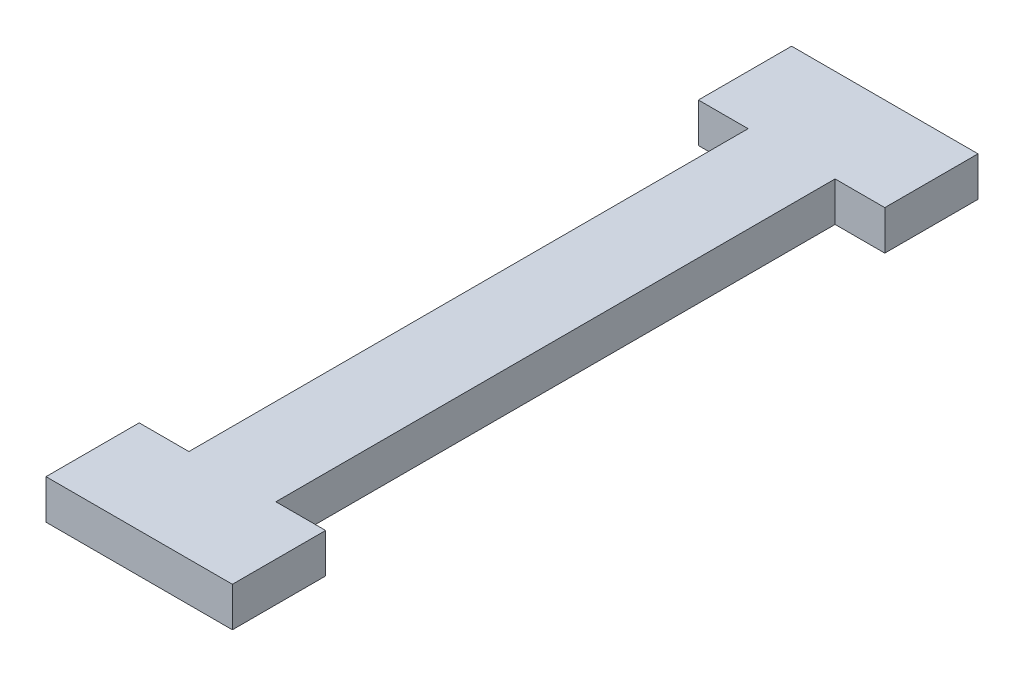
SolidWorks part; units mm, degrees
ref_plane "Front Plane" through (0, 0, 0) normal (0, 0, 1) x (1, 0, 0)
ref_plane "Top Plane" through (0, 0, 0) normal (0, 1, 0) x (1, 0, 0)
ref_plane "Right Plane" through (0, 0, 0) normal (1, 0, 0) x (0, 0, -1)
sketch "Sketch1" plane through (0, 0, 0) normal (0, 1, 0) x (1, 0, 0)
  line L0 (0, 0) -> (0, 60) construction
  line L1 (-15, 60) -> (15, 60)
  line L2 (15, 60) -> (15, 45)
  line L3 (15, 45) -> (7, 45)
  line L4 (7, 45) -> (7, -45)
  line L5 (7, 0) -> (0, 0) construction
  line L6 (-7, 45) -> (-7, -45)
  line L7 (-15, 45) -> (-7, 45)
  line L8 (-15, 60) -> (-15, 45)
  line L9 (15, -45) -> (7, -45)
  line L10 (15, -60) -> (15, -45)
  line L11 (-15, -60) -> (15, -60)
  line L12 (-15, -60) -> (-15, -45)
  line L13 (-15, -45) -> (-7, -45)
  point P17 (-7, 0)
  dimension "D1" = 60
  dimension "D2" = 7
  dimension "D3" = 15
  dimension "D4" = 15
extrude "Boss-Extrude1" add sketch "Sketch1" along normal blind 6.35
